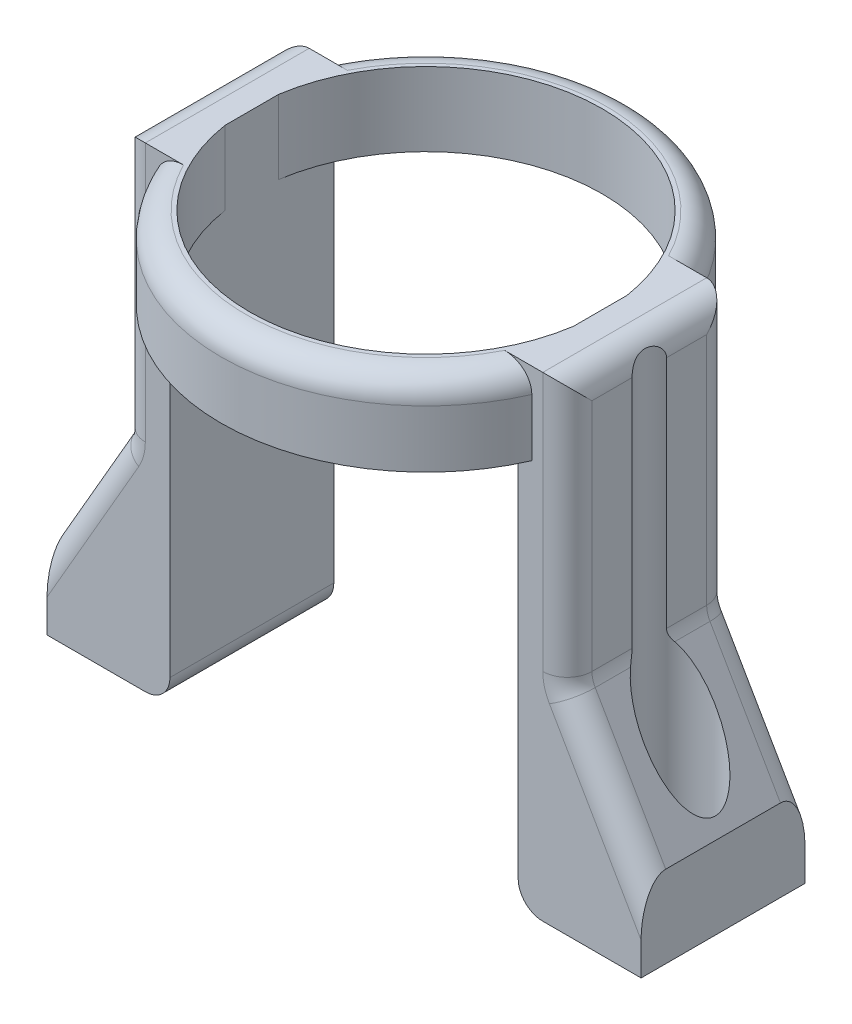
SolidWorks part; units mm, degrees
ref_plane "Спереди" through (0, 0, 0) normal (0, 0, 1) x (1, 0, 0)
ref_plane "Сверху" through (0, 0, 0) normal (0, 1, 0) x (1, 0, 0)
ref_plane "Справа" through (0, 0, 0) normal (1, 0, 0) x (0, 0, -1)
sketch "Эскиз1" plane through (0, 0, 0) normal (0, 1, 0) x (1, 0, 0)
  circle A0 centre (0, 0) radius 25
  circle A1 centre (0, 0) radius 21.5
  dimension "D1" = 50
  dimension "D2" = 43
extrude "Бобышка-Вытянуть1" add sketch "Эскиз1" along normal blind 10
sketch "Эскиз2" plane through (0, 10, 0) normal (0, -1, 0) x (-1, 0, 0)
  line L0 (31.3877, 0) -> (-43.976, 0) construction
  line L1 (0, -12.8215) -> (0, 11.0564) construction
  line L2 (-21.25, 10) -> (-27.25, 10)
  line L3 (-21.25, 10) -> (-21.25, -10)
  line L4 (-21.25, -10) -> (-27.25, -10)
  line L5 (-27.25, 10) -> (-27.25, -10)
  line L6 (-24.25, -10) -> (-24.25, 10) construction
  line L7 (-21.25, 0) -> (-27.25, 0) construction
  line L8 (21.25, -10) -> (27.25, -10)
  line L9 (27.25, 10) -> (27.25, -10)
  line L10 (21.25, 10) -> (27.25, 10)
  line L11 (21.25, 10) -> (21.25, -10)
  point P3 (-24.25, 0)
  dimension "D1" = 6
  dimension "D2" = 42.5
  dimension "D3" = 20
extrude "Бобышка-Вытянуть2" add sketch "Эскиз2" along normal blind 58
sketch "Эскиз3" plane through (0, -48, 0) normal (0, -1, 0) x (1, 0, 0)
  line L0 (0, 14.4616) -> (0, -9.395) construction
  line L1 (21.25, 10) -> (36.25, 10)
  line L2 (21.25, 10) -> (21.25, -10)
  line L3 (21.25, -10) -> (36.25, -10)
  line L4 (36.25, 10) -> (36.25, -10)
  line L5 (-21.25, -10) -> (-36.25, -10)
  line L6 (-36.25, 10) -> (-36.25, -10)
  line L7 (-21.25, 10) -> (-36.25, 10)
  line L8 (-21.25, 10) -> (-21.25, -10)
  dimension "D1" = 15
extrude "Бобышка-Вытянуть3" add sketch "Эскиз3" against normal blind 10
sketch "Эскиз4" plane through (0, -48, 0) normal (0, -1, 0) x (1, 0, 0)
  line L0 (-45.1049, 0) -> (52.4352, 0) construction
  line L1 (0, 13.0448) -> (0, -11.8624) construction
  circle A0 centre (31, 0) radius 2.3
  circle A1 centre (-31, 0) radius 2.3
  dimension "D1" = 62
  dimension "D2" = 4.6
extrude "Вырез-Вытянуть1" cut sketch "Эскиз4" against normal through all
chamfer "Фаска2" distance 9 angle 60 2 edges at (27.25, -38, 0) (-27.25, -38, 0) first distance on face at (31, -38, -2.3) first distance on face at (-31, -38, 2.3)
fillet "Скругление1" radius 3 16 edges at (31.75, -30.2058, -10) (31.75, -30.2058, 10) (-31.75, -30.2058, 10) (-31.75, -30.2058, -10) (27.25, 10, 0) (27.25, -6.2058, -10) (27.25, -22.4115, 0) (27.25, -6.2058, 10) (-27.25, 10, 0) (-27.25, -6.2058, 10) (-27.25, -22.4115, 0) (-27.25, -6.2058, -10) (0, 10, 25) (0, 10, -25) (-21.25, -48, 0) (21.25, -48, 0)
sketch "Эскиз5" plane through (0, 10, 0) normal (0, 1, 0) x (1, 0, 0)
  line L0 (-44.1555, 0) -> (41.7494, 0) construction
  line L1 (41.7494, 0) -> (0, 0) construction
  line L2 (0, 0) -> (0, 14.2862) construction
  circle A0 centre (31, 0) radius 4.3
  circle A1 centre (-31, 0) radius 4.3
  dimension "D1" = 8.6
  dimension "D2" = 62
extrude "Вырез-Вытянуть2" cut sketch "Эскиз5" against normal blind 55
chamfer "Фаска3" distance 1 angle 60 2 edges at (0, 0, -21.5) (0, 0, 21.5) first distance on face at (0, 5, -12.3846) first distance on face at (0, 5, 12.3846)
